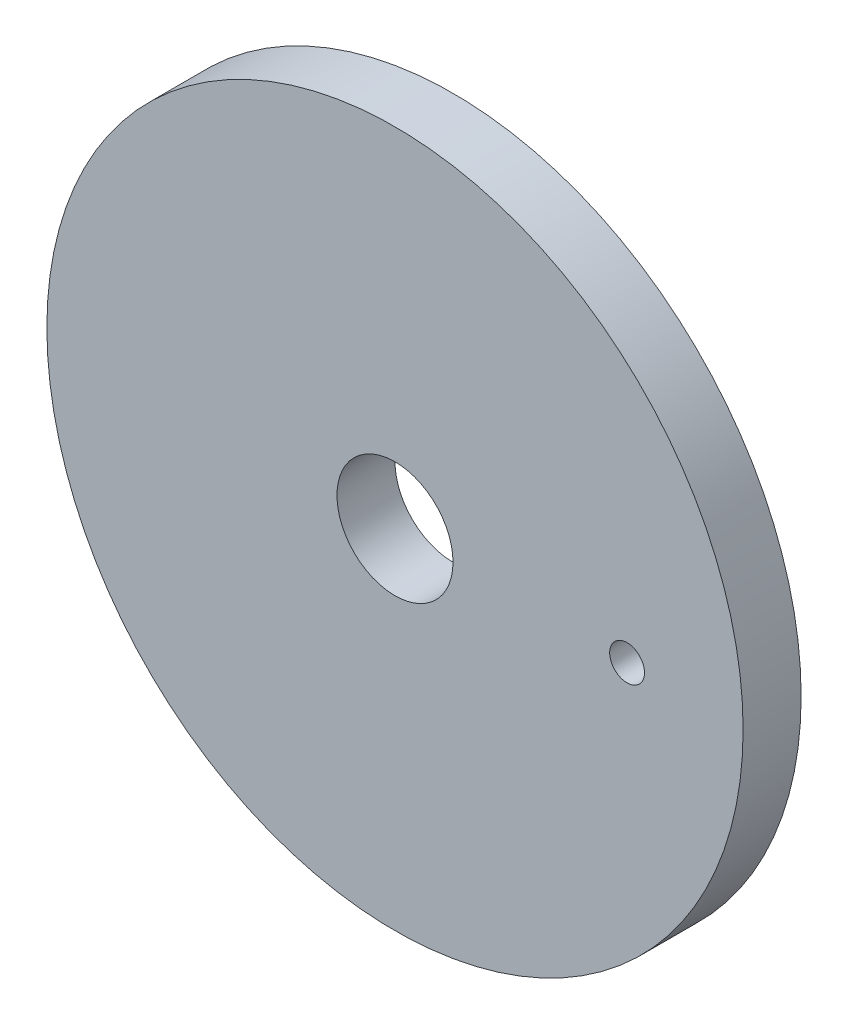
SolidWorks part; units mm, degrees
ref_plane "Front Plane" through (0, 0, 0) normal (0, 0, 1) x (1, 0, 0)
ref_plane "Top Plane" through (0, 0, 0) normal (0, 1, 0) x (1, 0, 0)
ref_plane "Right Plane" through (0, 0, 0) normal (1, 0, 0) x (0, 0, -1)
sketch "Sketch1" plane through (0, 0, 0) normal (0, 0, 1) x (1, 0, 0)
  circle A0 centre (0, 0) radius 76.2
extrude "round_plate" add sketch "Sketch1" along normal blind 12.7
sketch "Sketch2" plane through (0, 0, 0) normal (0, 0, 1) x (1, 0, 0)
  circle A0 centre (0, 0) radius 12.7
extrude "centre_bore" cut sketch "Sketch2" along normal through all
sketch "Sketch3" plane through (0, 0, 0) normal (0, 0, 1) x (1, 0, 0)
  circle A0 centre (50.8, 0) radius 3.81
extrude "seed_hole" cut sketch "Sketch3" along normal through all
ref_axis "Axis1" through (0, 0, 12.7) along (0, 0, -1)
ref_axis "Axis2" through (0, 0, 12.7) along (0, 0, -1)
